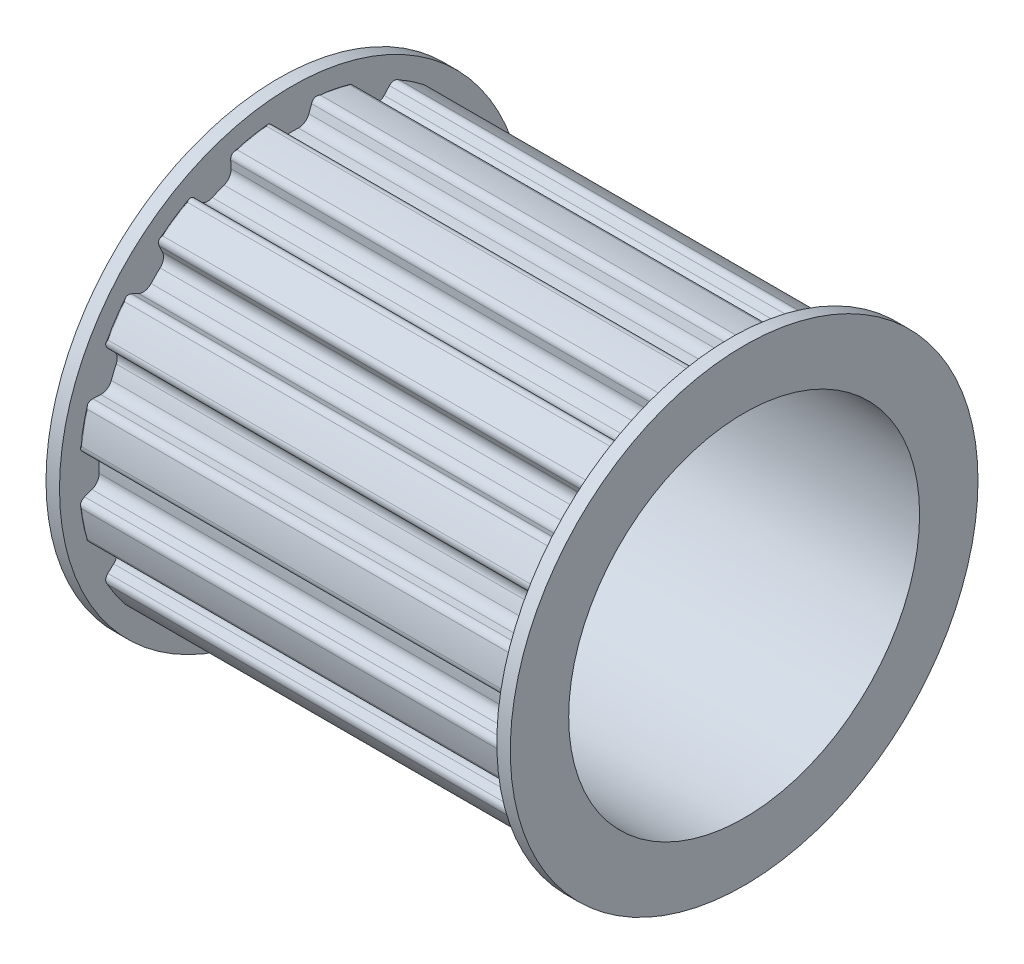
SolidWorks part; units mm, degrees
note: '?' marks a value the reader was unsure of.
material "尼龙 6/10"
ref_plane "前视基准面" through (0, 0, 0) normal (0, 0, 1) x (1, 0, 0)
ref_plane "上视基准面" through (0, 0, 0) normal (0, 1, 0) x (1, 0, 0)
ref_plane "右视基准面" through (0, 0, 0) normal (1, 0, 0) x (0, 0, -1)
sketch "草图1" plane through (0, 0, 0) normal (0, 0, 1) x (1, 0, 0)
  line L0 (0, 0) -> (64.8368, 0) construction
  line L1 (0, 6.3308) -> (0, 12.6616)
  line L2 (0.2, 31.654) -> (122.8, 31.654)
  line L3 (123, 31.454) -> (123, 25.3232)
  line L4 (0, 12.6616) -> (44, 12.6616) construction
  line L5 (44, 14.4211) -> (44, 23.5637)
  line L6 (123, 6.3308) -> (0, 6.3308)
  line L8 (5.9947, 257.6308) -> (12.0053, 257.6308) construction
  line L11 (9, 257.6308) -> (9, 6.3308) construction
  line L12 (44, 25.3232) -> (0, 25.3232) construction
  line L13 (123, 25.3232) -> (79, 25.3232) construction
  line L14 (79, 23.5637) -> (79, 14.4211)
  line L15 (79, 12.6616) -> (123, 12.6616) construction
  line L16 (61.5, 6.3308) -> (61.5, 31.654) construction
  line L17 (123, 12.6616) -> (123, 6.3308)
  line L18 (0, 25.3232) -> (0, 31.454)
  line L19 (44, 22.7909) -> (79, 22.7909) construction
  line L20 (44, 15.1939) -> (79, 15.1939) construction
  line L21 (123, 25.3232) -> (123, 22.7909) construction
  line L22 (123, 22.7909) -> (79, 22.7909) construction
  line L23 (79, 15.1939) -> (123, 15.1939) construction
  line L24 (123, 15.1939) -> (123, 12.6616) construction
  line L25 (79, 23.5637) -> (123, 25.3232)
  line L26 (44, 23.5637) -> (0, 25.3232)
  line L27 (44, 14.4211) -> (0, 12.6616)
  line L28 (79, 14.4211) -> (123, 12.6616)
  arc A0 (0, 31.454) -> (0.2, 31.654) centre (0.2, 31.454) cw
  arc A1 (123, 31.454) -> (122.8, 31.654) centre (122.8, 31.454) ccw
  dimension "r" = 0.2
  dimension "d" = 12.6616
  dimension "S" = 35
  dimension "S2" = 2.5323
  dimension "D3" = 2.29
  dimension "d2" = 50.6464
  dimension "D4" = 2.29
  dimension "d1" = 25.3232
  dimension "L" = 123
  dimension "B" = 123
  dimension "da" = 63.308
revolve "旋转1" add sketch "草图1" angle 360 about L0
chamfer "倒角1" distance 1 2 edges at (0, 0, 6.3308) (123, 0, 6.3308)
sketch "草图4" plane through (0, 0, 0) normal (-1, 0, 0) x (0, 0, 1)
  line L1 (-2.5, 5.8163) -> (2.5, 5.8163)
  line L2 (-2.5, 5.8163) -> (-2.5, 8.1163)
  line L3 (-2.5, 8.1163) -> (2.5, 8.1163)
  line L4 (2.5, 5.8163) -> (2.5, 8.1163)
  circle A0 centre (0, 0) radius 6.3308 construction
  dimension "键槽宽度" = 5
  dimension "t1" = 2.3
extrude "切除-拉伸1" [suppressed] cut sketch "草图4" against normal through all
fillet "圆角1" radius 2 4 edges at (79, 0, 23.5637) (44, 0, 14.4211) (44, 0, 23.5637) (79, 0, 14.4211)
fillet "圆角2" radius 2.5 2 edges at (123, 0, 12.6616) (0, 0, 12.6616)
ref_axis "基准轴1" through (-6.7721, 0, 0) along (1, 0, 0)?
sketch "草图5" plane through (0, 0, 0) normal (1, 0, 0) x (0, 0, -1)
  line L0 (0, 257.6308) -> (0, 6.3308) construction
  circle A0 centre (0, 18.9924) radius 3.7985
  dimension "D1" = 7.597
  dimension "D2" = 18.9924
extrude "切除-拉伸2" [suppressed] cut sketch "草图5" along normal through all
pattern_circular "阵列(圆周)1" [suppressed] count 4 over 360 about axis through (0, 0, 0) along (1, 0, 0)
sketch "草图6" plane through (0, 0, 0) normal (1, 0, 0) x (0, 0, -1)
  line L0 (0, 0) -> (0, 457.4471) construction
  line L1 (-2.9, 30.7389) -> (-2.5002, 29.6403)
  line L2 (-4.9966, 31.2571) -> (-17.4855, 65.5701)
  line L3 (4.9966, 31.2571) -> (17.4855, 65.5701)
  line L4 (2.9, 30.7389) -> (2.5002, 29.6403)
  arc A0 (0.9438, 28.5884) -> (-0.9438, 28.5884) centre (0, 0) ccw
  arc A1 (-3.987, 31.4019) -> (-4.9966, 31.2571) centre (0, 0) ccw
  arc A2 (-17.4855, 65.5701) -> (17.4855, 65.5701) centre (0, 0) cw
  arc A3 (-2.9, 30.7389) -> (-3.987, 31.4019) centre (-3.8585, 30.39) ccw
  arc A4 (3.987, 31.4019) -> (4.9966, 31.2571) centre (0, 0) cw
  arc A5 (2.9, 30.7389) -> (3.987, 31.4019) centre (3.8585, 30.39) cw
  arc A6 (-0.9438, 28.5884) -> (-2.5002, 29.6403) centre (-0.9966, 30.1876) cw
  arc A7 (2.5002, 29.6403) -> (0.9438, 28.5884) centre (0.9966, 30.1876) cw
  point P6 (0, 454.3971)
  point P18 (-2.095, 28.5272)
  point P21 (2.095, 28.5272)
  dimension "D1" = 31.654
  dimension "ra" = 1.02
  dimension "rf" = 1.6
  dimension "D4" = 28.604
  dimension "hg" = 3.05
  dimension "D2" = 1.02
  dimension "D3" = 36.5151
  dimension "bw" = 4.19
  dimension "angle" = 40
extrude "切除-拉伸3" cut sketch "草图6" along normal up to next
pattern_circular "阵列(圆周)3" count 16 over 360 about axis through (0, 0, 0) along (1, 0, 0) of "切除-拉伸3"
sketch "草图7" plane through (0, 0, 0) normal (-1, 0, 0) x (0, 0, 1)
  circle A1 centre (0, 0) radius 25.3232
  circle A2 centre (0, 0) radius 25.3232 construction
extrude "凸台-拉伸2" add sketch "草图7" against normal through all
sketch "草图8" plane through (0, 0, 0) normal (0, 1, 0) x (1, 0, 0)
  line L0 (122.8, 31.4019) -> (0.2, 31.4019) construction
  line L1 (65, -37.5323) -> (165, -37.5323)
  line L2 (65, -37.5323) -> (65, 37.4019)
  line L3 (65, 37.4019) -> (165, 37.4019)
  line L4 (165, -37.5323) -> (165, 37.4019)
  dimension "D1" = 65
  dimension "D2" = 100
  dimension "D3" = 6
extrude "切除-拉伸4" cut sketch "草图8" against normal mid plane 80
sketch "草图9" plane through (65, 0, 0) normal (1, 0, 0) x (0, 0, -1)
  circle A0 centre (0, 0) radius 34.654
  arc A1 (27.4858, 15.7005) -> (25.0237, 19.3853) centre (0, 0) ccw construction
  dimension "D1" = 3
extrude "凸台-拉伸3" add sketch "草图9" along normal blind 2
sketch "草图10" plane through (0, 0, 0) normal (-1, 0, 0) x (0, 0, 1)
  circle A0 centre (0, 0) radius 34.454
  arc A1 (27.6118, 15.0646) -> (24.4844, 19.7451) centre (0, 0) ccw construction
  dimension "D1" = 3
extrude "凸台-拉伸4" add sketch "草图10" along normal blind 2
sketch "草图11" plane through (-2, 0, 0) normal (-1, 0, 0) x (0, 0, 1)
  circle A0 centre (0, 0) radius 21.5
  dimension "D1" = 43
extrude "切除-拉伸5" cut sketch "草图11" against normal blind 10
sketch "草图12" plane through (67, 0, 0) normal (1, 0, 0) x (0, 0, -1)
  circle A0 centre (0, 0) radius 26
  dimension "D1" = 52
extrude "切除-拉伸6" cut sketch "草图12" against normal blind 40
sketch "草图13" plane through (8, 0, 0) normal (-1, 0, 0) x (0, 0, 1)
  circle A0 centre (0, 0) radius 2.5
  dimension "D1" = 5
extrude "切除-拉伸7" cut sketch "草图13" against normal through all
sketch "草图17" plane through (8, 0, 0) normal (1, 0, 0) x (0, 0, -1)
  circle A0 centre (0, 0) radius 11
  circle M4 centre (0, 0) radius 2.5
  dimension "D1" = 22
extrude "切除-拉伸9" cut sketch "草图17" along normal blind 1.5 contours A0 M4
sketch "草图15" plane through (27, 0, 0) normal (1, 0, 0) x (0, 0, -1)
  circle A0 centre (0, 0) radius 6 construction
  circle A1 centre (0, 6) radius 1.5
  circle A2 centre (6, 0) radius 1.5
  circle A3 centre (0, -6) radius 1.5
  circle A4 centre (-6, 0) radius 1.5
  dimension "D1" = 12
  dimension "D2" = 3
extrude "切除-拉伸8" cut sketch "草图15" against normal through all
sketch "草图18" plane through (8, 0, 0) normal (-1, 0, 0) x (0, 0, 1)
  circle A0 centre (0, 0) radius 21.5
  circle A1 centre (0, 0) radius 21.5 construction
equation "\"D1@草图5\" = \"d2@草图1\" / 2 - \"d1@草图1\" / 2 - \"S2@草图1\" * 2"
equation "\"D2@草图5\" = \"d1@草图1\" / 2 + \"S2@草图1\" + \"D1@草图5\" / 2"
equation "\"D1@草图6\" = \"da@草图1\" / 2"
equation "\"D2@草图6\" = \"ra@草图6\""
equation "\"D4@草图6\" = \"da@草图1\" / 2 - \"hg@草图6\""
